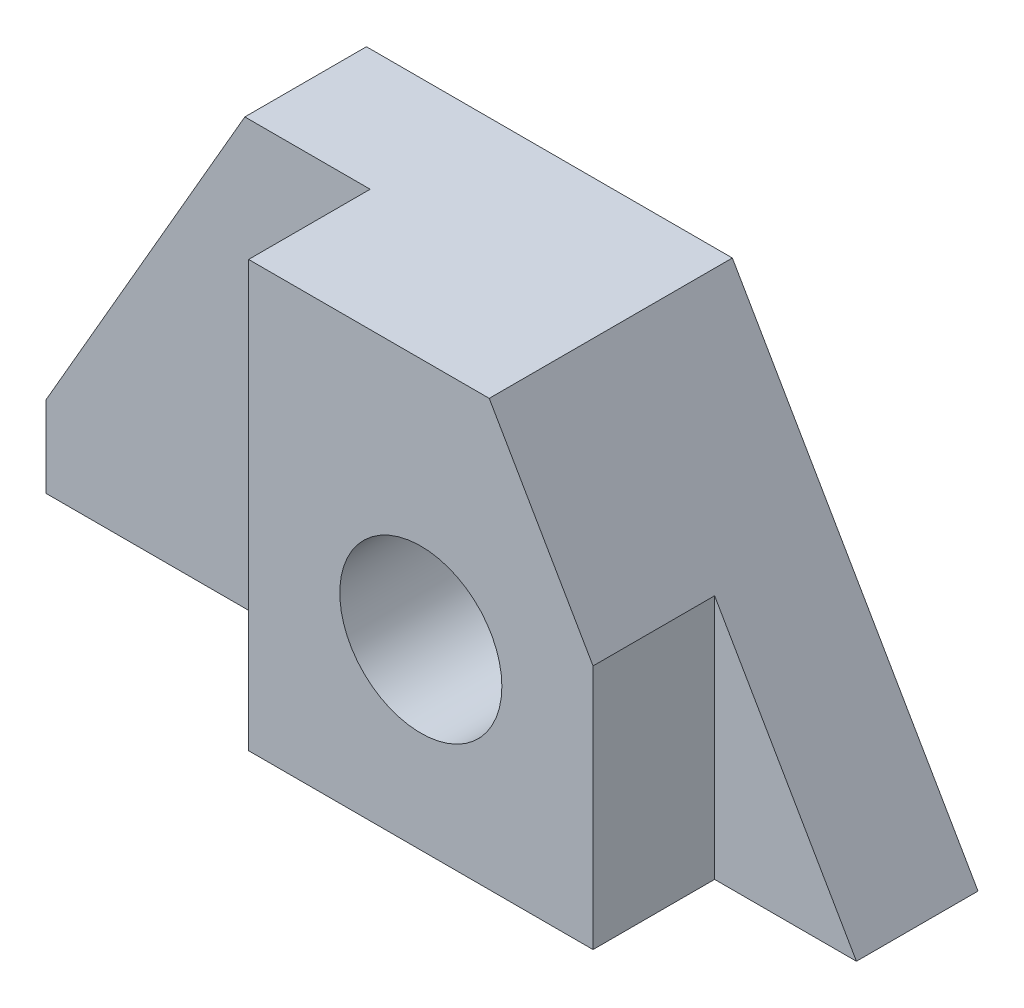
SolidWorks part; units mm, degrees
ref_plane "Front Plane" through (0, 0, 0) normal (0, 0, 1) x (1, 0, 0)
ref_plane "Top Plane" through (0, 0, 0) normal (0, 1, 0) x (1, 0, 0)
ref_plane "Right Plane" through (0, 0, 0) normal (1, 0, 0) x (0, 0, -1)
sketch "Sketch1" plane through (0, 0, 0) normal (0, 0, 1) x (1, 0, 0)
  line L0 (-106.8224, 0) -> (101.6, 0) construction
  line L1 (-89.3012, 12.7) -> (-89.3012, 0)
  line L2 (-89.3012, 0) -> (37.6988, 0)
  line L3 (37.6988, 0) -> (-0.7961, 66.675)
  line L4 (-0.7961, 66.675) -> (-58.1388, 66.675)
  line L5 (-58.1388, 66.675) -> (-89.3012, 12.7)
  line L6 (-38.5012, 66.675) -> (-38.5012, 0)
  line L7 (15.4738, 38.4948) -> (15.4738, 0)
  line L8 (37.6988, -17.5343) -> (37.6988, 56.6363) construction
  line L9 (-89.3012, -20.736) -> (-89.3012, 83.8199) construction
  line L10 (-11.5137, -9.0821) -> (-11.5137, 44.4622) construction
  circle A0 centre (-11.5137, 28.575) radius 12.7
  dimension "D9" = 25.4
  dimension "D1" = 127
  dimension "D2" = 12.7
  dimension "D3" = 30
  dimension "D4" = 30
  dimension "D5" = 66.675
  dimension "D6" = 22.225
  dimension "D7" = 53.975
  dimension "D8" = 77.7875
  dimension "D10" = 28.575
extrude "Boss-Extrude1" add sketch "Sketch1" along normal blind 19.05 contours L6 L4 L5 L1 L2 | L3 L7 L2 region at (-58.9425, 28.2686, 0) region at (22.8821, 12.8316, 0)
extrude "Boss-Extrude2" add sketch "Sketch1<3>" along normal blind 38.1 contours L7 L3 L4 L6 L2 A0 region at (-37.6434, 33.3375, 0)
sketch "Sketch1<3>" plane through (0, 0, 0) normal (0, 0, 1) x (1, 0, 0) same geometry as "Sketch1"
